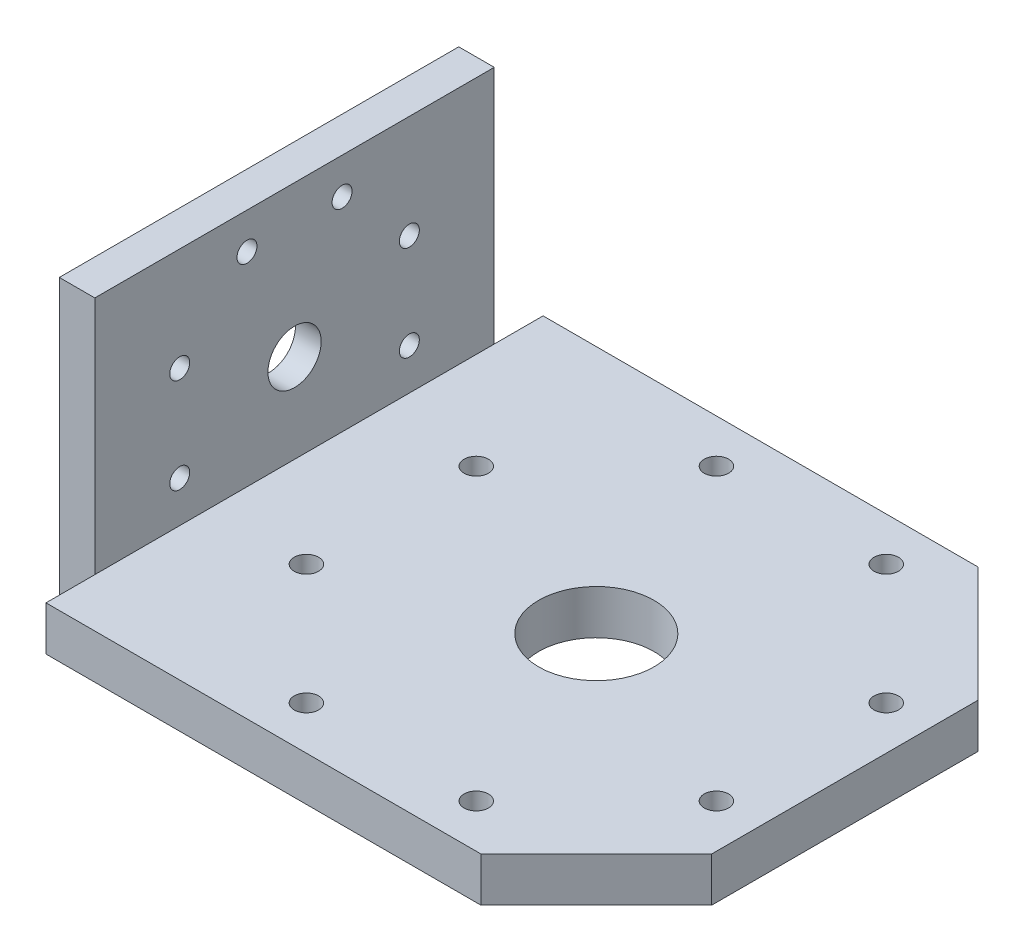
SolidWorks part; units mm, degrees
ref_plane "Front Plane" through (0, 0, 0) normal (0, 0, 1) x (1, 0, 0)
ref_plane "Top Plane" through (0, 0, 0) normal (0, 1, 0) x (1, 0, 0)
ref_plane "Right Plane" through (0, 0, 0) normal (1, 0, 0) x (0, 0, -1)
ref_plane "PL_Back_Plate_base" through (-76, 0, 0) normal (1, 0, 0) x (0, 0, -1)
sketch "SK_Back_Plate" plane through (-76, 0, 0) normal (1, 0, 0) x (0, 0, -1)
  line L0 (45, -36) -> (45, 34)
  line L1 (45, 34) -> (-45, 34)
  line L2 (-45, 34) -> (-45, -36)
  line L3 (-45, -36) -> (45, -36)
  circle A0 centre (25.8686, 10.7151) radius 2.25
  circle A1 centre (10.7151, 25.8686) radius 2.25
  circle A2 centre (-10.7151, 25.8686) radius 2.25
  circle A3 centre (-25.8686, 10.7151) radius 2.25
  circle A4 centre (-25.8686, -10.7151) radius 2.25
  circle A5 centre (-10.7151, -25.8686) radius 2.25
  circle A6 centre (10.7151, -25.8686) radius 2.25
  circle A7 centre (25.8686, -10.7151) radius 2.25
  circle A8 centre (0, 0) radius 6
  dimension "D9_SK_Back_Plate" = 4.5
  dimension "D12_SK_Back_Plate" = 4.5
  dimension "D15_SK_Back_Plate" = 4.5
  dimension "D18_SK_Back_Plate" = 4.5
  dimension "D21_SK_Back_Plate" = 4.5
  dimension "D24_SK_Back_Plate" = 4.5
  dimension "D27_SK_Back_Plate" = 4.5
  dimension "D30_SK_Back_Plate" = 4.5
  dimension "D33_SK_Back_Plate" = 12
  dimension "P1" = 45
  dimension "P2" = 36
  dimension "P3" = 45
  dimension "P4" = 34
  dimension "P5" = 45
  dimension "P6" = 34
  dimension "P7" = 45
  dimension "P8" = 36
  dimension "P10" = 25.8686
  dimension "P11" = 10.7151
  dimension "P13" = 10.7151
  dimension "P14" = 25.8686
  dimension "P16" = 10.7151
  dimension "P17" = 25.8686
  dimension "P19" = 25.8686
  dimension "P20" = 10.7151
  dimension "P22" = 25.8686
  dimension "P23" = 10.7151
  dimension "P25" = 10.7151
  dimension "P26" = 25.8686
  dimension "P28" = 10.7151
  dimension "P29" = 25.8686
  dimension "P31" = 25.8686
  dimension "P32" = 10.7151
extrude "Back_Plate" add sketch "SK_Back_Plate" along normal blind 8
ref_plane "PL_Roll_Pilot_Recess_base" through (-76, 0, 0) normal (1, 0, 0) x (0, 0, -1)
sketch "SK_Roll_Pilot_Recess" plane through (-76, 0, 0) normal (1, 0, 0) x (0, 0, -1)
  circle A0 centre (0, 0) radius 22.15
  dimension "D1_SK_Roll_Pilot_Recess" = 44.3
extrude "Roll_Pilot_Recess" cut sketch "SK_Roll_Pilot_Recess" along normal blind 2.2
ref_plane "PL_Medial_Plate_base" through (0, -30, 0) normal (0, 1, 0) x (1, 0, 0)
sketch "SK_Medial_Plate" plane through (0, -30, 0) normal (0, 1, 0) x (1, 0, 0)
  line L0 (-68, 56) -> (30, 56)
  line L1 (30, 56) -> (56, 30)
  line L2 (56, 30) -> (56, -30)
  line L3 (56, -30) -> (30, -56)
  line L4 (30, -56) -> (-68, -56)
  line L5 (-68, -56) -> (-68, 56)
  circle A0 centre (46.194, 19.1342) radius 2.75
  circle A1 centre (19.1342, 46.194) radius 2.75
  circle A2 centre (-19.1342, 46.194) radius 2.75
  circle A3 centre (-46.194, 19.1342) radius 2.75
  circle A4 centre (-46.194, -19.1342) radius 2.75
  circle A5 centre (-19.1342, -46.194) radius 2.75
  circle A6 centre (19.1342, -46.194) radius 2.75
  circle A7 centre (46.194, -19.1342) radius 2.75
  circle A8 centre (0, 0) radius 13
  dimension "D13_SK_Medial_Plate" = 5.5
  dimension "D16_SK_Medial_Plate" = 5.5
  dimension "D19_SK_Medial_Plate" = 5.5
  dimension "D22_SK_Medial_Plate" = 5.5
  dimension "D25_SK_Medial_Plate" = 5.5
  dimension "D28_SK_Medial_Plate" = 5.5
  dimension "D31_SK_Medial_Plate" = 5.5
  dimension "D34_SK_Medial_Plate" = 5.5
  dimension "D37_SK_Medial_Plate" = 26
  dimension "P1" = 68
  dimension "P2" = 56
  dimension "P3" = 30
  dimension "P4" = 56
  dimension "P5" = 56
  dimension "P6" = 30
  dimension "P7" = 56
  dimension "P8" = 30
  dimension "P9" = 30
  dimension "P10" = 56
  dimension "P11" = 68
  dimension "P12" = 56
  dimension "P14" = 46.194
  dimension "P15" = 19.1342
  dimension "P17" = 19.1342
  dimension "P18" = 46.194
  dimension "P20" = 19.1342
  dimension "P21" = 46.194
  dimension "P23" = 46.194
  dimension "P24" = 19.1342
  dimension "P26" = 46.194
  dimension "P27" = 19.1342
  dimension "P29" = 19.1342
  dimension "P30" = 46.194
  dimension "P32" = 19.1342
  dimension "P33" = 46.194
  dimension "P35" = 46.194
  dimension "P36" = 19.1342
extrude "Medial_Plate" add sketch "SK_Medial_Plate" along normal blind 10
equation "\"Roll_face_x\" = -76"
equation "\"Pitch_rear_y\" = -20"
equation "\"Plate_t\" = 10"
